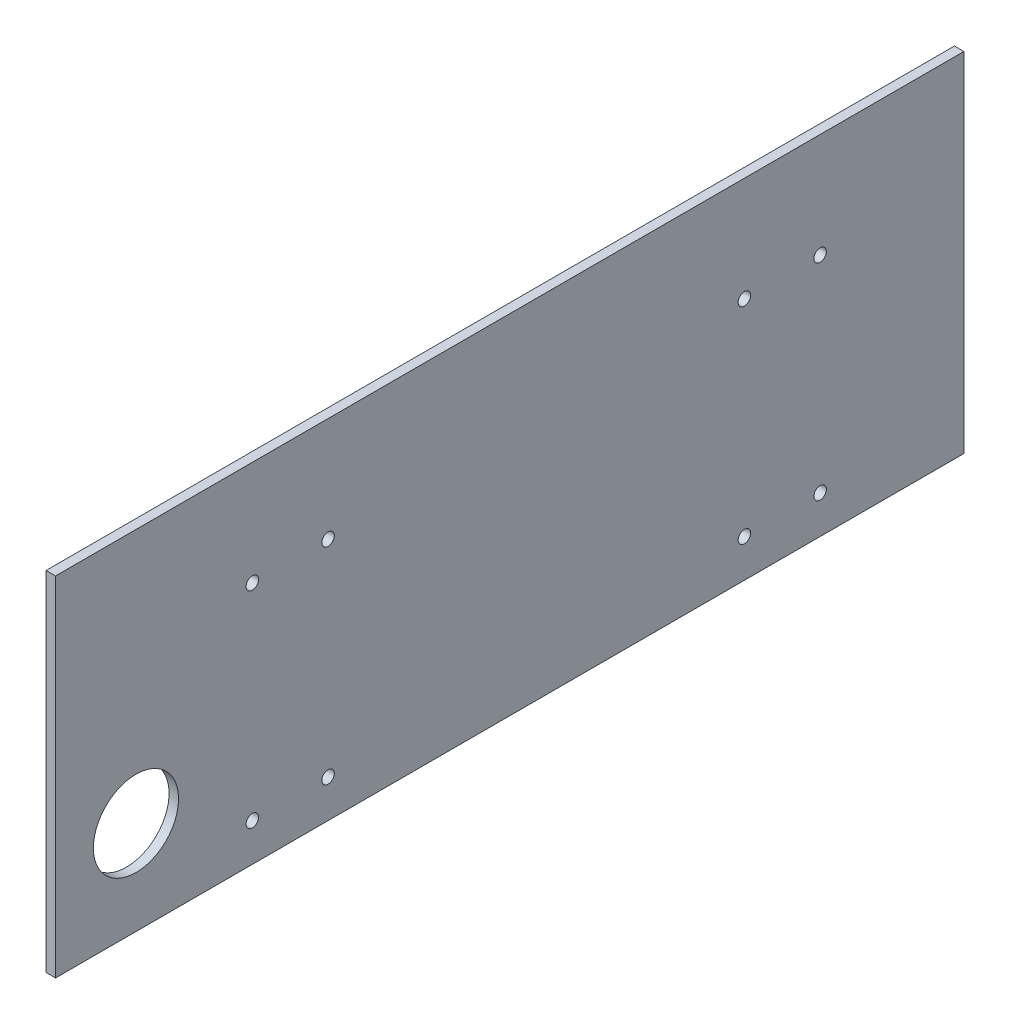
SolidWorks part; units mm, degrees
ref_plane "Front Plane" through (0, 0, 0) normal (0, 0, 1) x (1, 0, 0)
ref_plane "Top Plane" through (0, 0, 0) normal (0, 1, 0) x (1, 0, 0)
ref_plane "Right Plane" through (0, 0, 0) normal (1, 0, 0) x (0, 0, -1)
sketch "Sketch1" plane through (0, 0, 0) normal (1, 0, 0) x (0, 0, -1)
  line L1 (-152.4, -58.42) -> (152.4, -58.42)
  line L2 (-152.4, -58.42) -> (-152.4, 58.42)
  line L3 (-152.4, 58.42) -> (152.4, 58.42)
  line L4 (152.4, -58.42) -> (152.4, 58.42)
  line L5 (-152.4, -58.42) -> (152.4, 58.42) construction
  line L6 (-152.4, 58.42) -> (152.4, -58.42) construction
  point P0 (0, 0)
  dimension "D1" = 116.84
  dimension "D2" = 304.8
extrude "Boss-Extrude1" add sketch "Sketch1" along normal blind 3.175
sketch "Sketch2" plane through (3.175, 0, 0) normal (1, 0, 0) x (0, 0, -1)
  line L0 (-152.4, -58.42) -> (-86.36, -58.42)
  line L1 (-152.4, -58.42) -> (152.4, -58.42) construction
  line L2 (-86.36, -58.42) -> (-86.36, -45.72)
  line L3 (-86.36, -45.72) -> (-60.96, -45.72)
  circle A0 centre (-86.36, -45.72) radius 2.0955
  circle A1 centre (-60.96, -45.72) radius 2.0955
  circle A2 centre (104.14, -45.72) radius 2.0955
  circle A3 centre (78.74, -45.72) radius 2.0955
  circle A4 centre (104.14, 23.368) radius 2.0955
  circle A5 centre (78.74, 23.368) radius 2.0955
  circle A6 centre (-60.96, 23.368) radius 2.0955
  circle A7 centre (-86.36, 23.368) radius 2.0955
  dimension "D4" = 4.191
  dimension "D5" = 4.191
  dimension "D1" = 66.04
  dimension "D2" = 12.7
  dimension "D3" = 25.4
  dimension "D6" = 2
  dimension "D7" = 2
extrude "Cut-Extrude1" cut sketch "Sketch2" against normal up to surface (3.175 mm away) contours L3 A0 L2 | L2 A0 L3 | A1 | A2 | A3 | A7 | A6 | A5 | A4 region at (3.175, -45.4235, 86.6565) region at (3.175, -43.6838, 60.96) region at (3.175, -46.6094, 85.4706) region at (3.175, -45.72, -104.14) region at (3.175, -45.72, -78.74) region at (3.175, 23.368, -104.14) region at (3.175, 23.368, -78.74) region at (3.175, 23.368, 60.96) region at (3.175, 23.368, 86.36) up to face at (0, 0, 0)
sketch "Sketch3" plane through (0, 0, 0) normal (-1, 0, 0) x (0, 0, 1)
  line L0 (152.4, -58.42) -> (152.4, -26.9875)
  line L1 (152.4, 58.42) -> (152.4, -58.42) construction
  line L2 (152.4, -26.9875) -> (125.4125, -26.9875)
  circle A0 centre (125.4125, -26.9875) radius 14.2875
  dimension "D3" = 28.575
  dimension "D1" = 31.4325
  dimension "D2" = 26.9875
extrude "Cut-Extrude2" cut sketch "Sketch3" against normal blind 3.175 contours A0
